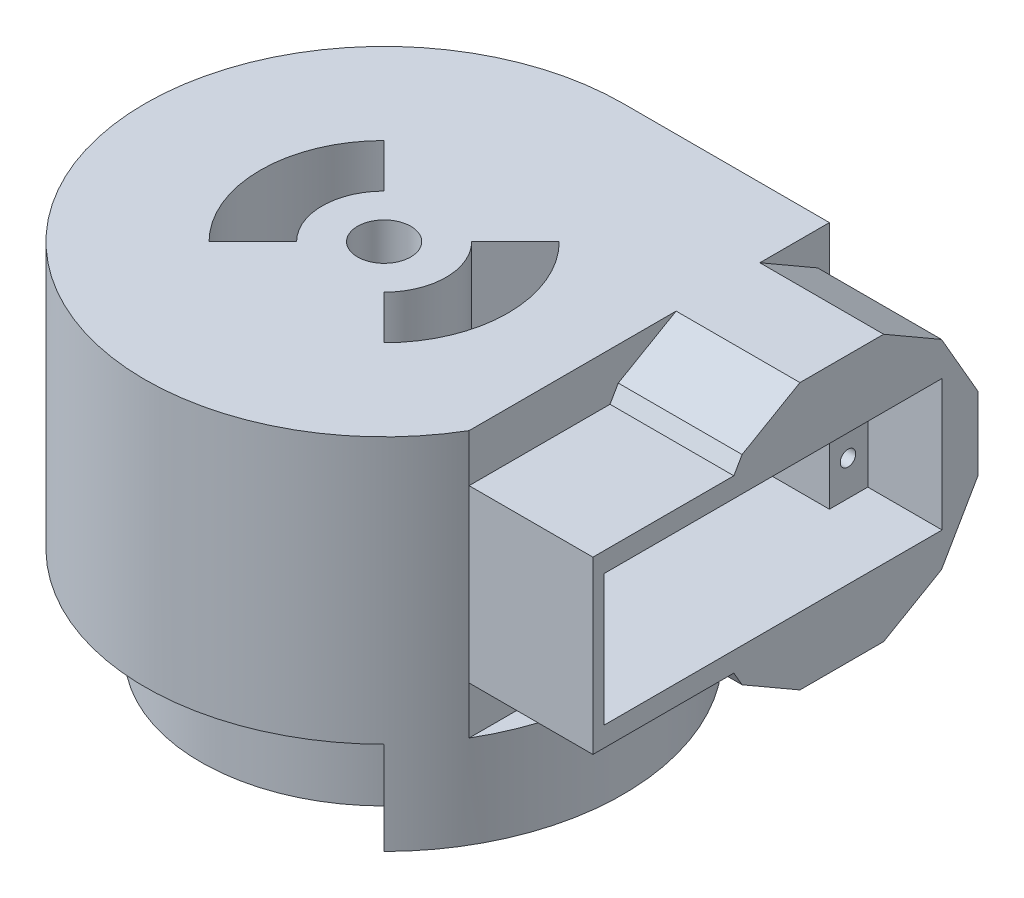
SolidWorks part; units mm, degrees
ref_plane "Front Plane" through (0, 0, 0) normal (0, 0, 1) x (1, 0, 0)
ref_plane "Top Plane" through (0, 0, 0) normal (0, 1, 0) x (1, 0, 0)
ref_plane "Right Plane" through (0, 0, 0) normal (1, 0, 0) x (0, 0, -1)
sketch "Sketch1" plane through (0, 0, 0) normal (0, 1, 0) x (1, 0, 0)
  line L0 (0, 38.625) -> (53.2973, 38.625)
  line L1 (53.2973, 38.625) -> (53.2973, -19.575)
  line L2 (53.2973, -19.575) -> (33.2973, -19.575)
  line L3 (0, 60.3307) -> (0, -56.6529) construction
  arc A0 (0, 38.625) -> (33.2973, -19.575) centre (0, 0) ccw
  dimension "D1" = 20
  dimension "D2" = 38.625
  dimension "D7" = 58.2
extrude "Boss-Extrude1" add sketch "Sketch1" along normal blind 43
sketch "Sketch4" plane through (0, 0, 0) normal (0, -1, 0) x (1, 0, 0)
  line L0 (-38.625, 0) -> (53.2973, 0) construction
  line L1 (53.2973, 19.575) -> (53.2973, -38.625) construction
  line L2 (20.948, 20.948) -> (27.312, 27.312)
  line L3 (20.948, -20.948) -> (27.312, -27.312)
  line L4 (20.948, -20.948) -> (0, 0) construction
  line L5 (0, 0) -> (20.948, 20.948) construction
  arc A0 (33.2973, 19.575) -> (0, -38.625) centre (0, 0) ccw construction
  arc A1 (20.948, 20.948) -> (20.948, -20.948) centre (0, 0) ccw
  arc A4 (27.312, -27.312) -> (27.312, 27.312) centre (0, 0) ccw
  dimension "D1" = 45
  dimension "D2" = 45
  dimension "D3" = 9
extrude "Boss-Extrude2" add sketch "Sketch4" along normal blind 15
sketch "Sketch5" plane through (53.2973, 0, 0) normal (1, 0, 0) x (0, 0, -1)
  line L0 (9.525, 43) -> (9.525, 0) construction
  line L1 (-19.575, 43) -> (38.625, 43) construction
  line L2 (-19.575, 0) -> (38.625, 0) construction
  line L3 (-19.575, 21.5) -> (38.625, 21.5) construction
  line L4 (-19.575, 43) -> (-19.575, 0) construction
  line L5 (38.625, 43) -> (38.625, 0) construction
  line L6 (-14.575, 26.45) -> (-14.575, 16.55) construction
  line L7 (-10.975, 11.5) -> (30.025, 11.5) construction
  line L8 (-10.975, 11.5) -> (-10.975, 31.5) construction
  line L9 (-10.975, 31.5) -> (30.025, 31.5) construction
  line L10 (30.025, 11.5) -> (30.025, 31.5) construction
  line L11 (-10.975, 11.5) -> (30.025, 31.5) construction
  line L12 (-10.975, 31.5) -> (30.025, 11.5) construction
  line L13 (33.625, 26.45) -> (33.625, 16.55) construction
  line L14 (-11.575, 10.9) -> (-11.575, 32.1)
  line L15 (-11.575, 32.1) -> (30.625, 32.1)
  line L16 (30.625, 32.1) -> (30.625, 10.9)
  line L17 (30.625, 10.9) -> (-11.575, 10.9)
  line L18 (-11.575, 10.9) -> (-17.775, 10.9)
  line L19 (-17.775, 10.9) -> (-17.775, 32.1)
  line L20 (-17.775, 32.1) -> (-11.575, 32.1)
  line L21 (30.625, 32.1) -> (36.825, 32.1)
  line L22 (36.825, 32.1) -> (36.825, 10.9)
  line L23 (36.825, 10.9) -> (30.625, 10.9)
  circle A0 centre (-14.575, 26.45) radius 1.25
  circle A1 centre (-14.575, 16.55) radius 1.25
  circle A2 centre (33.625, 16.55) radius 1.25
  circle A3 centre (33.625, 26.45) radius 1.25
  circle A4 centre (19.625, 21.5) radius 6 construction
  point P12 (9.525, 21.5)
  point P25 (-14.575, 21.5)
  point P27 (33.625, 21.5)
  point P38 (9.525, 32.1)
  point P39 (-17.775, 21.5)
  dimension "D8" = 2.5
  dimension "D9" = 2.5
  dimension "D10" = 2.5
  dimension "D11" = 2.5
  dimension "D14" = 12
  dimension "D13" = 17.2
  dimension "D1" = 9.9
  dimension "D2" = 9.9
  dimension "D3" = 24.1
  dimension "D4" = 24.1
  dimension "D5" = 0.6
  dimension "D6" = 20
  dimension "D7" = 54.6
  dimension "D12" = 0.6
  dimension "D15" = 41
extrude "Cut-Extrude1" cut sketch "Sketch5" against normal blind 41 contours L17 L16 L15 L14 region at (53.2973, 21.5, -9.525)
extrude "Cut-Extrude2" cut sketch "Sketch5<5>" against normal blind 12 contours L20 L19 L18 L14 A1 A0 | L23 L22 L21 L16 A3 A2 region at (53.2973, 21.5, 14.6831) region at (53.2973, 21.5, -33.7331)
sketch "Sketch5<5>" plane through (53.2973, 0, 0) normal (1, 0, 0) x (0, 0, -1) same geometry as "Sketch5"
extrude "Cut-Extrude3" cut sketch "Sketch5<6>" against normal blind 35 contours A3 | A2 | A0 | A1 region at (53.2973, 26.45, 14.575) region at (53.2973, 16.55, 14.575) region at (53.2973, 16.55, -33.625) region at (53.2973, 26.45, -33.625)
sketch "Sketch5<6>" plane through (53.2973, 0, 0) normal (1, 0, 0) x (0, 0, -1) same geometry as "Sketch5"
sketch "Sketch6" plane through (0, -15, 0) normal (0, -1, 0) x (1, 0, 0)
  line L0 (0, -38.625) -> (0, 38.625) construction
  line L1 (38.625, 0) -> (-38.625, 0) construction
  line L2 (7.0711, 7.0711) -> (14.1421, 14.1421)
  line L3 (7.0711, -7.0711) -> (14.1421, -14.1421)
  line L4 (0, 0) -> (7.0711, 7.0711) construction
  line L5 (7.0711, -7.0711) -> (0, 0) construction
  line L6 (-7.0711, -7.0711) -> (-14.1421, -14.1421)
  line L7 (-7.0711, 7.0711) -> (-14.1421, 14.1421)
  circle A0 centre (0, 0) radius 4.3
  arc A1 (27.312, 27.312) -> (0, -38.625) centre (0, 0) ccw construction
  arc A2 (27.312, -27.312) -> (27.312, 27.312) centre (0, 0) ccw construction
  arc A3 (7.0711, 7.0711) -> (7.0711, -7.0711) centre (0, 0) cw
  arc A4 (14.1421, -14.1421) -> (14.1421, 14.1421) centre (0, 0) ccw
  arc A5 (-14.1421, -14.1421) -> (-14.1421, 14.1421) centre (0, 0) cw
  arc A6 (-7.0711, 7.0711) -> (-7.0711, -7.0711) centre (0, 0) ccw
  dimension "D1" = 8.6
  dimension "D3" = 10
  dimension "D4" = 10
  dimension "D2" = 45
  dimension "D5" = 45
extrude "Cut-Extrude4" cut sketch "Sketch6" against normal through all both and the other way through all
sketch "Sketch7" plane through (41.2973, 0, 0) normal (1, 0, 0) x (0, 0, -1)
  line L0 (30.625, 32.1) -> (30.625, 10.9) construction
  line L1 (25.625, 18.1) -> (35.625, 18.1)
  line L2 (25.625, 18.1) -> (25.625, 24.9)
  line L3 (25.625, 24.9) -> (35.625, 24.9)
  line L4 (35.625, 18.1) -> (35.625, 24.9)
  line L5 (25.625, 18.1) -> (35.625, 24.9) construction
  line L6 (25.625, 24.9) -> (35.625, 18.1) construction
  point P0 (30.625, 21.5)
  dimension "D1" = 6.8
  dimension "D2" = 10
extrude "Cut-Extrude5" cut sketch "Sketch7" against normal through all from offset 5 offset against normal yes
sketch "Sketch9" plane through (53.2973, 0, 0) normal (1, 0, 0) x (0, 0, -1)
  line L0 (14.7301, 43.5) -> (4.5199, 37.6051)
  line L1 (26.5199, -0.5) -> (36.7301, 5.3949)
  line L2 (36.7301, 5.3949) -> (42.625, 15.6051)
  line L3 (42.625, 15.6051) -> (42.625, 27.3949)
  line L4 (42.625, 27.3949) -> (36.7301, 37.6051)
  line L5 (36.7301, 37.6051) -> (26.5199, 43.5)
  line L6 (26.5199, 43.5) -> (14.7301, 43.5)
  line L7 (4.5199, 37.6051) -> (-1.375, 27.3949)
  line L8 (-1.375, 27.3949) -> (-1.375, 15.6051)
  line L9 (-1.375, 15.6051) -> (4.5199, 5.3949)
  line L10 (4.5199, 5.3949) -> (14.7301, -0.5)
  line L11 (14.7301, -0.5) -> (26.5199, -0.5)
  line L12 (38.625, 43) -> (38.625, 0) construction
  line L13 (-19.575, 43) -> (-19.575, 35.3)
  line L14 (-19.575, 43) -> (-19.575, 0) construction
  line L15 (-19.575, 35.3) -> (3.189, 35.3)
  line L16 (-19.575, 43) -> (13.8641, 43)
  line L17 (27.3859, 43) -> (38.625, 43)
  line L18 (-19.575, 43) -> (38.625, 43) construction
  line L19 (38.625, 43) -> (38.625, 34.3231)
  line L20 (-19.575, 7.7) -> (3.189, 7.7)
  line L21 (-19.575, 7.7) -> (-19.575, 0)
  line L22 (-19.575, 0) -> (13.8641, 0)
  line L23 (-19.575, 0) -> (38.625, 0) construction
  line L24 (-17.775, 32.1) -> (36.825, 32.1) construction
  line L25 (36.825, 10.9) -> (-17.775, 10.9) construction
  line L26 (38.625, 8.6769) -> (38.625, 0)
  line L27 (38.625, 0) -> (27.3859, 0)
  line L28 (38.625, 8.6769) -> (38.625, 34.3231)
  line L30 (-19.575, 21.5) -> (38.625, 21.5) construction
  line L33 (30.625, 32.1) -> (30.625, 10.9) construction
  circle A0 centre (20.625, 21.5) radius 22 construction
  point P44 (0, 0)
  point P46 (0, 0)
  point P49 (0, 0)
  point P50 (21.0044, 21.5)
  line M2 (-19.575, 0) -> (38.625, 0)
  line M3 (38.625, 0) -> (38.625, 43)
  line M4 (38.625, 43) -> (-19.575, 43)
  line M5 (-19.575, 43) -> (-19.575, 0)
  dimension "D1" = 44
  dimension "D2" = 3.2
  dimension "D3" = 3.2
  dimension "D4" = 10
extrude "Cut-Extrude9" cut sketch "Sketch9" against normal up to vertex (20 mm away) contours L5 L4 M3 M4 | L15 L7 L0 M5 M4 | L20 L10 L9 M5 M2 | L2 L1 M2 M3 region at (53.2973, 39.4198, 5.7858) region at (53.2973, 40.5847, -35.0462) region at (53.2973, 3.5802, 5.7858) region at (53.2973, 2.4153, -35.0462) up to point (33.2973, 0, 19.575)
extrude "Boss-Extrude3" add sketch "Sketch9<7>" against normal up to vertex (53.2973 mm away) contours L3 L4 L2 M3 region at (53.2973, 21.5, -40.3782) up to point (0, 43, -38.625)
sketch "Sketch9<7>" plane through (53.2973, 0, 0) normal (1, 0, 0) x (0, 0, -1) same geometry as "Sketch9"
chamfer "Chamfer1" distance 10 angle 45 1 edges at (0, 21.5, -38.625)
